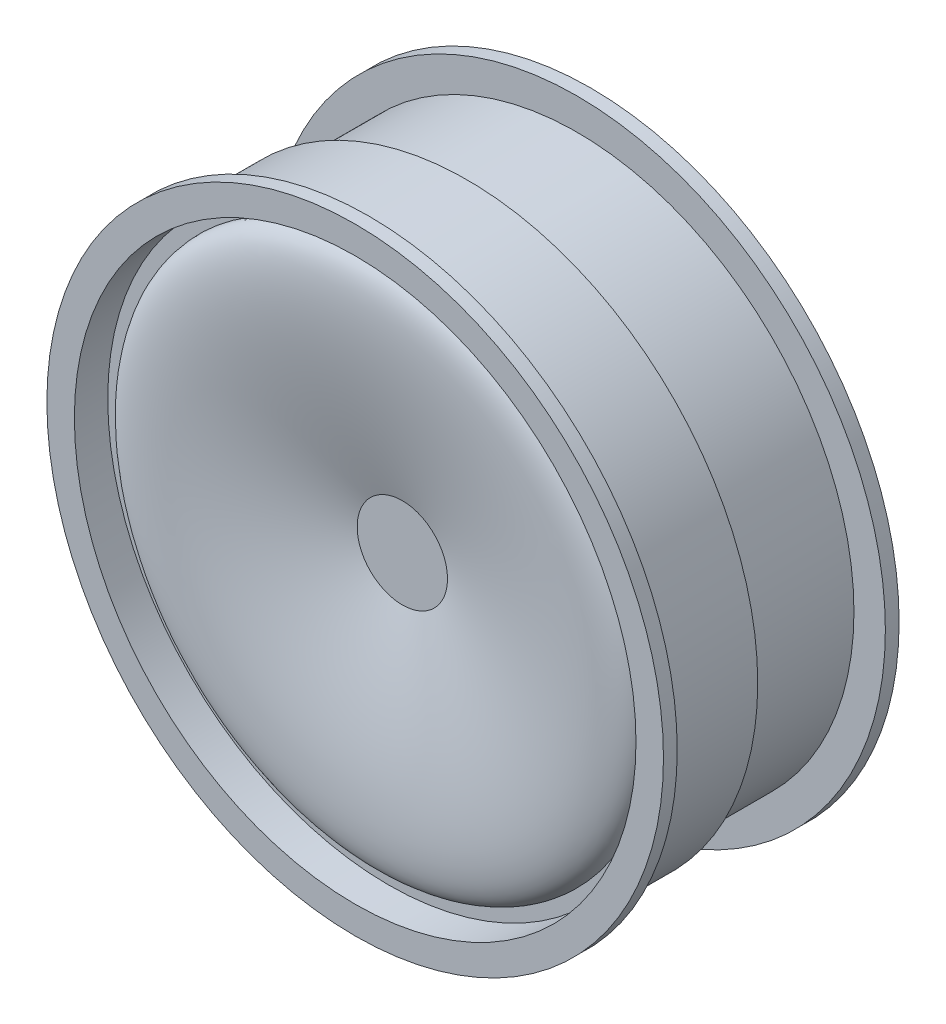
SolidWorks part; units mm, degrees
ref_plane "Front Plane" through (0, 0, 0) normal (0, 0, 1) x (1, 0, 0)
ref_plane "Top Plane" through (0, 0, 0) normal (0, 1, 0) x (1, 0, 0)
ref_plane "Right Plane" through (0, 0, 0) normal (1, 0, 0) x (0, 0, -1)
sketch "Sketch1" plane through (0, 0, 0) normal (1, 0, 0) x (0, 0, -1)
  line L0 (0, 5.75) -> (-7.5, 30) construction
  line L1 (-7.5, 30) -> (-4, 34) construction
  line L2 (-4, 34) -> (-1.7538, 34) construction
  line L3 (2.2088, 7.5) -> (-4.75, 30) construction
  line L4 (-4.75, 30) -> (-2, 32.5) construction
  line L5 (-2, 32.5) -> (1.2462, 32.5) construction
  line L7 (0, 0) -> (2.2088, 0)
  line L8 (2.2088, 0) -> (2.2088, 7.5)
  line L9 (-1.7538, 34) -> (-1.7538, 35.75)
  line L10 (-1.7538, 35.75) -> (-6.0038, 35.75)
  line L11 (-6.0038, 35.75) -> (-6.0038, 39.25)
  line L12 (-6.0038, 39.25) -> (-4.2538, 39.25)
  line L13 (-4.2538, 39.25) -> (-4.2538, 37)
  line L14 (-4.2538, 37) -> (8.2462, 37)
  line L15 (8.2462, 37) -> (8.2462, 35.25)
  line L16 (8.2462, 35.25) -> (22.2462, 35.25)
  line L17 (22.2462, 35.25) -> (22.2462, 39.25)
  line L18 (22.2462, 39.25) -> (23.9962, 39.25)
  line L19 (23.9962, 39.25) -> (23.9962, 32.5)
  line L20 (23.9962, 32.5) -> (1.2462, 32.5)
  line L21 (0, 5.75) -> (0, 0)
  spline S0 degree 3 poles (0, 5.75) (-7.5, 30) (-4, 34) (-1.7538, 34) knots 0 0 0 0 1 1 1 1
  spline S1 degree 3 poles (2.2088, 7.5) (-4.75, 30) (-2, 32.5) (1.2462, 32.5) knots 0 0 0 0 1 1 1 1
  dimension "D1" = 1.5
  dimension "D2" = 6.75
  dimension "D3" = 6.0038
  dimension "D4" = 30
  dimension "D5" = 12.5
  dimension "D6" = 1.75
  dimension "D7" = 1.75
  dimension "D8" = 4.25
  dimension "D9" = 4
  dimension "D10" = 22.75
  dimension "D11" = 7.5
  dimension "D12" = 5.75
  dimension "D13" = 2.75
  dimension "D14" = 30
  dimension "D15" = 32.5
  dimension "D16" = 7.5
  dimension "D17" = 4
  dimension "D18" = 2
sketch "Sketch2" plane through (0, 0, 0) normal (0, 0, 1) x (1, 0, 0)
  line L1 (0, 34.0388) -> (0, -0.4527) construction
  line L2 (1.875, 33.9871) -> (2.5727, 11.348)
  line L4 (-1.875, 33.9871) -> (-2.5727, 11.348)
  line L5 (30.3712, 15.3698) -> (11.114, 3.446)
  line L6 (28.4962, 18.6174) -> (8.5413, 7.902)
  line L7 (28.4962, -18.6174) -> (8.5413, -7.902)
  line L8 (30.3712, -15.3698) -> (11.114, -3.446)
  line L9 (-1.875, -33.9871) -> (-2.5727, -11.348)
  line L10 (1.875, -33.9871) -> (2.5727, -11.348)
  line L11 (-30.3712, -15.3698) -> (-11.114, -3.446)
  line L12 (-28.4962, -18.6174) -> (-8.5413, -7.902)
  line L13 (-28.4962, 18.6174) -> (-8.5413, 7.902)
  line L14 (-30.3712, 15.3698) -> (-11.114, 3.446)
  circle A0 centre (0, 0) radius 3.75
  arc A1 (-4.0572, 9.14) -> (-5.8869, 8.0836) centre (0, 0) ccw
  arc A2 (2.5727, 11.348) -> (4.0572, 9.14) centre (5.0715, 11.425) ccw
  arc A3 (-2.5727, 11.348) -> (-4.0572, 9.14) centre (-5.0715, 11.425) cw
  arc A4 (1.875, 33.9871) -> (-1.875, 33.9871) centre (0, 0) ccw
  arc A5 (30.3712, 15.3698) -> (28.4962, 18.6174) centre (0, 0) ccw
  arc A6 (11.114, 3.446) -> (9.944, 1.0564) centre (12.4301, 1.3205) ccw
  arc A7 (8.5413, 7.902) -> (5.8869, 8.0836) centre (7.3586, 10.1045) cw
  arc A8 (28.4962, -18.6174) -> (30.3712, -15.3698) centre (0, 0) ccw
  arc A9 (8.5413, -7.902) -> (5.8869, -8.0836) centre (7.3586, -10.1045) ccw
  arc A10 (11.114, -3.446) -> (9.944, -1.0564) centre (12.4301, -1.3205) cw
  arc A11 (-1.875, -33.9871) -> (1.875, -33.9871) centre (0, 0) ccw
  arc A12 (-2.5727, -11.348) -> (-4.0572, -9.14) centre (-5.0715, -11.425) ccw
  arc A13 (2.5727, -11.348) -> (4.0572, -9.14) centre (5.0715, -11.425) cw
  arc A14 (-30.3712, -15.3698) -> (-28.4962, -18.6174) centre (0, 0) ccw
  arc A15 (-11.114, -3.446) -> (-9.944, -1.0564) centre (-12.4301, -1.3205) ccw
  arc A16 (-8.5413, -7.902) -> (-5.8869, -8.0836) centre (-7.3586, -10.1045) cw
  arc A17 (-28.4962, 18.6174) -> (-30.3712, 15.3698) centre (0, 0) ccw
  arc A18 (-8.5413, 7.902) -> (-5.8869, 8.0836) centre (-7.3586, 10.1045) ccw
  arc A19 (-11.114, 3.446) -> (-9.944, 1.0564) centre (-12.4301, 1.3205) cw
  arc A20 (-9.944, 1.0564) -> (-9.944, -1.0564) centre (0, 0) ccw
  arc A21 (-5.8869, -8.0836) -> (-4.0572, -9.14) centre (0, 0) ccw
  arc A22 (4.0572, -9.14) -> (5.8869, -8.0836) centre (0, 0) ccw
  arc A23 (5.8869, 8.0836) -> (4.0572, 9.14) centre (0, 0) ccw
  arc A24 (9.944, -1.0564) -> (9.944, 1.0564) centre (0, 0) ccw
  point P7 (0, 34)
  point P12 (2.625, 9.6493)
  point P15 (-2.625, 9.6493)
  point P59 (0, 0)
  dimension "D1" = 7.5
  dimension "D2" = 20
  dimension "D5" = 2.5
  dimension "D6" = 34.0388
  dimension "D3" = 3.75
  dimension "D4" = 5.25
  dimension "D7" = 34.4915
  dimension "D8" = 6
ref_axis "Axis1" through (0, 0, 0) along (0, 0, -1)
revolve "Revolve2" add sketch "Sketch1" angle 360 about L7
